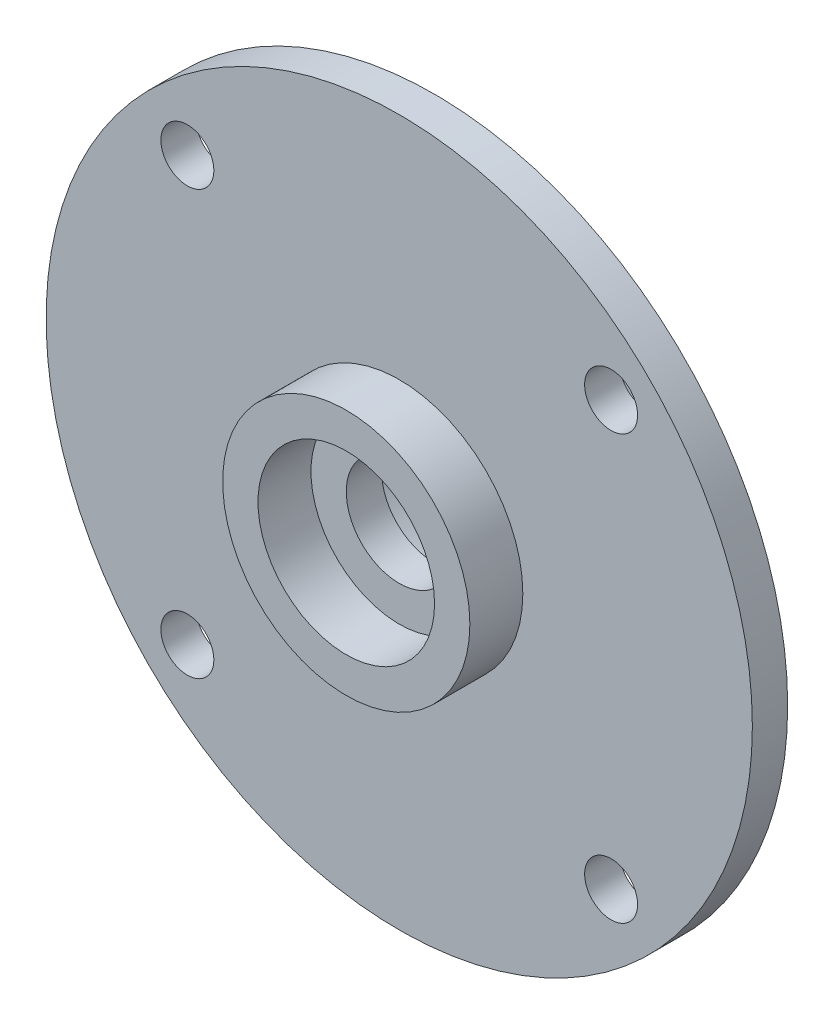
SolidWorks part; units mm, degrees
ref_plane "前视基准面" through (0, 0, 0) normal (0, 0, 1) x (1, 0, 0)
ref_plane "上视基准面" through (0, 0, 0) normal (0, 1, 0) x (1, 0, 0)
ref_plane "右视基准面" through (0, 0, 0) normal (1, 0, 0) x (0, 0, -1)
other "Configuration Table"
sketch "草图1" plane through (0, 0, 0) normal (0, 0, 1) x (1, 0, 0)
  line L5 (-15, 15) -> (15, -15) construction
  line L6 (-15, -15) -> (15, 15) construction
  circle A0 centre (-12, 12) radius 1.5
  circle A1 centre (12, 12) radius 1.5
  circle A2 centre (12, -12) radius 1.5
  circle A3 centre (-12, -12) radius 1.5
  circle A4 centre (0, 0) radius 3
  circle A5 centre (0, 0) radius 20
  point P0 (0, 0)
  point P17 (0, 0)
  dimension "D4" = 4
extrude "凸台-拉伸1" add sketch "草图1" along normal blind 2
sketch "草图2" plane through (0, 0, 2) normal (0, 0, 1) x (1, 0, 0)
  circle A0 centre (0, 0) radius 7
  circle A1 centre (0, 0) radius 5
  dimension "D1" = 14
  dimension "D2" = 10
sketch "草图3" plane through (0, 0, 0) normal (0, 0, -1) x (-1, 0, 0)
  circle A0 centre (0, 0) radius 11
  circle A1 centre (0, 0) radius 7.5
  dimension "D1" = 22
  dimension "D2" = 15
extrude "凸台-拉伸2" add sketch "草图3" along normal blind 5
extrude "凸台-拉伸3" add sketch "草图2" along normal blind 3
